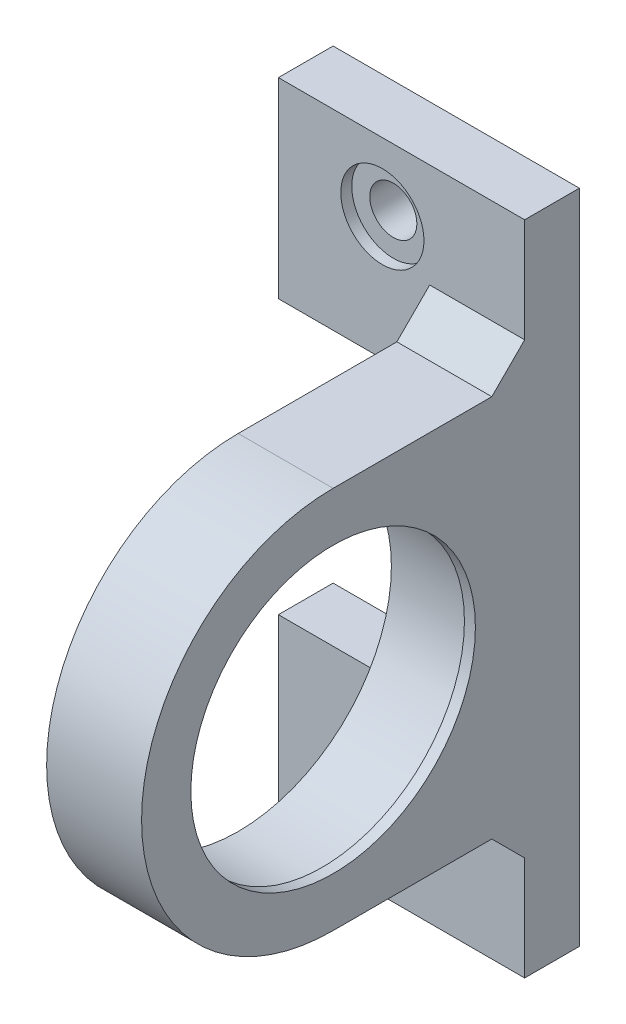
SolidWorks part; units mm, degrees
ref_plane "前视基准面" through (0, 0, 0) normal (0, 0, 1) x (1, 0, 0)
ref_plane "上视基准面" through (0, 0, 0) normal (0, 1, 0) x (1, 0, 0)
ref_plane "右视基准面" through (0, 0, 0) normal (1, 0, 0) x (0, 0, -1)
sketch "草图2" plane through (0, 0, 0) normal (0, 0, 1) x (1, 0, 0)
  line L0 (-14.7736, 24.3382) -> (-14.7736, -35.6618)
  line L1 (-14.7736, -35.6618) -> (30.2264, -35.6618)
  line L2 (7.7264, -35.6618) -> (7.7264, -18.1618)
  line L3 (21.55, -18.1618) -> (-6.0971, -18.1618)
  line L4 (-6.0971, -18.1618) -> (-6.0971, 6.8382)
  line L5 (-6.0971, 6.8382) -> (21.55, 6.8382)
  line L6 (7.7264, 6.8382) -> (7.7264, 24.3382)
  line L7 (30.2264, 24.3382) -> (-14.7736, 24.3382)
  line L8 (7.7264, 28.8603) -> (7.7264, -39.8897) construction
  line L9 (21.55, -18.1618) -> (21.55, 6.8382)
  line L10 (30.2264, 24.3382) -> (30.2264, -35.6618)
  line L11 (-18.1559, -5.6618) -> (33.2411, -5.6618) construction
  line L12 (44.0218, -5.6618) -> (44.0218, 26.2521) construction
  point P16 (-6.0971, -5.6618)
  point P17 (-14.7736, -5.6618)
  dimension "D1" = 45
  dimension "D2" = 25
  dimension "D3" = 60
extrude "凸台-拉伸2" add sketch "草图2" along normal blind 5 contours L6 L7 L0 L1 L2 L3 L4 L5 | L10 L7 L6 L5 L9 L3 L2 L1 region at (-3.5236, 23.6974, 0) region at (18.9764, 23.6974, 0)
sketch "草图4" plane through (0, 0, 5) normal (0, 0, 1) x (1, 0, 0)
  line L0 (-18.165, -5.6618) -> (33.9165, -5.6618) construction
  line L1 (-14.7736, 24.3382) -> (-14.7736, -35.6618) construction
  line L2 (-14.7736, -23.1618) -> (-6.0971, -23.1618)
  line L3 (-14.7736, -23.1618) -> (-14.7736, 11.8382)
  line L4 (-14.7736, 11.8382) -> (-6.0971, 11.8382)
  line L5 (-6.0971, -23.1618) -> (-6.0971, 11.8382)
  line L6 (-6.0971, -18.1618) -> (-6.0971, 6.8382) construction
  line L7 (7.7264, -39.813) -> (7.7264, 28.1228) construction
  line L8 (30.2264, 11.8382) -> (21.55, 11.8382)
  line L9 (21.55, -23.1618) -> (21.55, 11.8382)
  line L10 (30.2264, -23.1618) -> (21.55, -23.1618)
  line L11 (30.2264, -23.1618) -> (30.2264, 11.8382)
  point P17 (-14.7736, -5.6618)
  dimension "D1" = 35
extrude "凸台-拉伸15" add sketch "草图4" along normal blind 35
sketch "草图5" plane through (-14.7736, 0, 0) normal (-1, 0, 0) x (0, 0, 1)
  line L0 (0, -5.6618) -> (40, -5.6618)
  line L1 (0, 24.3382) -> (0, -35.6618) construction
  line L2 (40, 11.8382) -> (40, -23.1618) construction
  line L3 (22.5, 11.8382) -> (40, 11.8382)
  line L4 (40, 11.8382) -> (40, -23.1618)
  line L5 (40, -23.1618) -> (22.5, -23.1618)
  circle A0 centre (22.5, -5.6618) radius 17.5
  line M5 (5, -23.1618) -> (40, -23.1618)
  line M6 (40, -23.1618) -> (40, 11.8382)
  line M7 (40, 11.8382) -> (5, 11.8382)
  dimension "D1" = 35
extrude "切除-拉伸1" cut sketch "草图5" against normal blind 45 contours A0 M5 M6 | A0 M6 M7 region at (-14.7736, 7.9293, 36.0911) region at (-14.7736, -19.2528, 36.0911)
sketch "草图6" plane through (-14.7736, 0, 0) normal (-1, 0, 0) x (0, 0, 1)
  circle A0 centre (22.5, -5.6618) radius 14
  dimension "D1" = 28
extrude "切除-拉伸2" cut sketch "草图6" against normal blind 45
fillet "圆角1" radius 5 4 edges at (-6.0971, 6.8382, 2.5) (21.55, 6.8382, 2.5) (-6.0971, -18.1618, 2.5) (21.55, -18.1618, 2.5)
sketch "草图7" plane through (-6.0971, 0, 0) normal (1, 0, 0) x (0, 0, -1)
  circle A0 centre (-22.5, -5.6618) radius 15
  circle A1 centre (-22.5, -5.6618) radius 13
extrude "凸台-拉伸16" add sketch "草图7" against normal blind 1
sketch "草图8" plane through (21.55, 0, 0) normal (-1, 0, 0) x (0, 0, 1)
  circle A0 centre (22.5, -5.6618) radius 15
  circle A1 centre (22.5, -5.6618) radius 10
sketch "草图9" plane through (0, 0, 5) normal (0, 0, 1) x (1, 0, 0)
  line L0 (7.7264, 24.3382) -> (7.7264, -35.6618)
  line L13 (30.2264, 24.3382) -> (-14.7736, 24.3382) construction
  line L14 (-14.7736, -35.6618) -> (30.2264, -35.6618) construction
sketch "草图11" plane through (0, 0, 5) normal (0, 0, 1) x (1, 0, 0)
  line L0 (-14.7736, 18.0882) -> (30.2264, 18.0882)
  line L1 (-14.7736, 24.3382) -> (-14.7736, 11.8382) construction
  line L2 (30.2264, 24.3382) -> (30.2264, 11.8382) construction
  line L3 (7.7264, 24.3382) -> (7.7264, -35.6618) construction
  line L4 (30.2264, 24.3382) -> (-14.7736, 24.3382) construction
  line L5 (-14.7736, -35.6618) -> (30.2264, -35.6618) construction
  line L6 (7.7264, -5.6618) -> (45.6912, -5.6618) construction
  line L10 (-14.7736, -29.4118) -> (30.2264, -29.4118)
  line L11 (-14.7736, -23.1618) -> (-14.7736, -35.6618) construction
  point P4 (-1.7736, 18.0882)
  point P16 (-1.7736, -29.4118)
  point P18 (17.2264, -29.4118)
  point P25 (17.2264, 18.0882)
  dimension "D1" = 13
split "分割1" trim tools "草图9" bodies to split 111 resulting bodies 117 118
delete or keep bodies "实体-删除/保留 2" type delete bodies bodies 117
hole_wizard "打孔尺寸(%根据六角头螺)栓 全螺纹的类型1" positions "3D草图2" profile "草图13" counterbore size "M4" standard "GB"
sketch3d "3D草图2"
  point P0 (17.2264, 18.0882, 5)
  point P3 (17.2264, -29.4118, 5)
sketch "草图13" plane through (17.2264, 18.0882, 5) normal (1, 0, 0) x (0, -1, 0)
  line L0 (0, 0) -> (0, 6.2919)
  line L1 (0, 6.2919) -> (2.15, 5)
  line L2 (2.15, 5) -> (2.15, 1)
  line L3 (2.15, 1) -> (3.8, 1)
  line L4 (3.8, 1) -> (3.8, 0)
  line L5 (3.8, 0) -> (0, 0)
  line L10 (0, 6.2919) -> (-2.15, 5) construction
  line L11 (0, -6.35) -> (0, 107.95) construction
  dimension "孔直径" = 4.3
  dimension "孔深度" = 5
  dimension "柱形沉头孔直径" = 7.6
  dimension "柱形沉头孔深度" = 1
  dimension "导头角度" = 118
ref_plane "基准面1" through (30.2264, 0, 0) normal (1, 0, 0) x (0, 0, -1)
sketch "草图14" plane through (30.2264, 0, 0) normal (1, 0, 0) x (0, 0, -1)
  circle A1 centre (-22.5, -5.6618) radius 14 construction
  circle A3 centre (-22.5, -5.6618) radius 14
extrude "拉伸-薄壁1" add sketch "草图14" against normal blind 1 thin thin type one direction reverse wall 1
chamfer "倒角1" distance 3 angle 45 2 edges at (25.8882, -23.1618, 5) (25.8882, 11.8382, 5)
